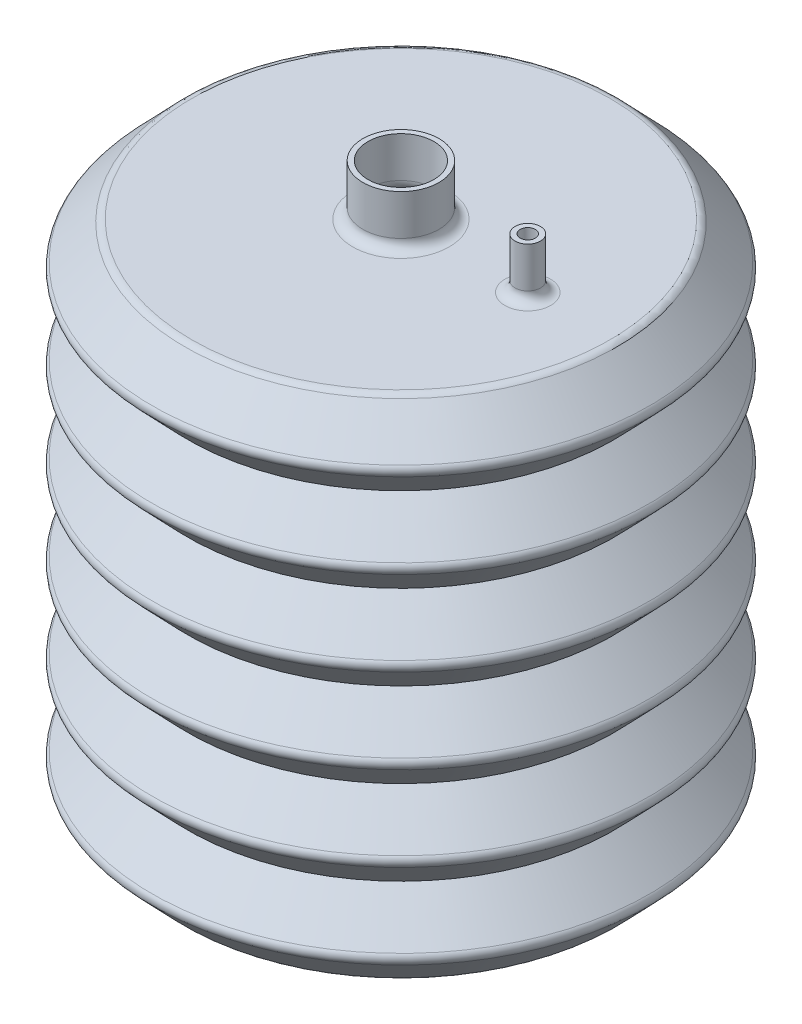
SolidWorks part; units mm, degrees
material "Perspex (TM) Folha de Acrílico GS Fundido"
ref_plane "Plano frontal" through (0, 0, 0) normal (0, 0, 1) x (1, 0, 0)
ref_plane "Plano superior" through (0, 0, 0) normal (0, 1, 0) x (1, 0, 0)
ref_plane "Plano direito" through (0, 0, 0) normal (1, 0, 0) x (0, 0, -1)
sketch "Esboço1" plane through (0, 0, 0) normal (1, 0, 0) x (0, 0, -1)
  line L0 (0, 0) -> (0, 121.08) construction
  line L1 (0, 0) -> (41.1476, 0)
  line L2 (42.5903, 0.6149) -> (49.0408, 7.3342)
  line L3 (49.0408, 9.3325) -> (42, 16.6667)
  line L4 (50, 8.3333) -> (42, 8.3333) construction
  line L5 (42, 16.6667) -> (49.0408, 24.0008)
  line L6 (49.0408, 25.9992) -> (42, 33.3333)
  line L7 (50, 25) -> (42, 25) construction
  line L8 (42, 33.3333) -> (49.0408, 40.6675)
  line L9 (49.0408, 42.6658) -> (42, 50)
  line L10 (50, 41.6667) -> (42, 41.6667) construction
  line L11 (42, 50) -> (49.0408, 57.3342)
  line L12 (49.0408, 59.3325) -> (42, 66.6667)
  line L13 (50, 58.3333) -> (42, 58.3333) construction
  line L14 (41.2158, 100) -> (9.5, 100)
  line L15 (42, 66.6667) -> (49.0408, 74.0008)
  line L16 (49.0408, 75.9992) -> (42, 83.3333)
  line L17 (50, 75) -> (42, 75) construction
  line L18 (42, 83.3333) -> (49.0408, 90.6675)
  line L19 (49.0408, 92.6658) -> (42.5431, 99.4343)
  line L20 (50, 91.6667) -> (42, 91.6667) construction
  line L21 (0, 100) -> (0, 0)
  line L22 (7.5, 102) -> (7.5, 110)
  line L23 (7.5, 110) -> (0, 110)
  line L24 (0, 110) -> (0, 100)
  arc A0 (49.0408, 90.6675) -> (49.0408, 92.6658) centre (48, 91.6667) ccw
  arc A1 (49.0408, 74.0008) -> (49.0408, 75.9992) centre (48, 75) ccw
  arc A2 (49.0408, 57.3342) -> (49.0408, 59.3325) centre (48, 58.3333) ccw
  arc A3 (49.0408, 40.6675) -> (49.0408, 42.6658) centre (48, 41.6667) ccw
  arc A4 (49.0408, 25.9992) -> (49.0408, 24.0008) centre (48, 25) cw
  arc A5 (49.0408, 7.3342) -> (49.0408, 9.3325) centre (48, 8.3333) ccw
  arc A6 (41.2158, 100) -> (42.5431, 99.4343) centre (41.2158, 98.1601) cw
  arc A7 (9.5, 100) -> (7.5, 102) centre (9.5, 102) cw
  arc A8 (41.1476, 0) -> (42.5903, 0.6149) centre (41.1476, 2) ccw
  point P18 (42, 100)
  point P51 (42, 0)
  dimension "D3" = 2
  dimension "D6" = 2
  dimension "D7" = 2
  dimension "D10" = 2
  dimension "D1" = 6
  dimension "D2" = 100
  dimension "D4" = 8
  dimension "D5" = 100
  dimension "D8" = 10
  dimension "D9" = 15
revolve "Revolução1" add sketch "Esboço1" angle 360 about L0
sketch "Esboço2" plane through (0, 100, 0) normal (0, 1, 0) x (1, 0, 0)
  circle A0 centre (25, 0) radius 2.5
  point P2 (0, 0)
  point P4 (0, 0)
  dimension "D1" = 5
  dimension "D2" = 25
extrude "Ressalto-extrusão1" add sketch "Esboço2" along normal blind 10
fillet "Filete1" radius 2 1 edges at (25, 100, 2.5)
shell "Casca2" thickness 1 removed face at (25, 110, 2.5) removed face at (0, 110, -7.5)
